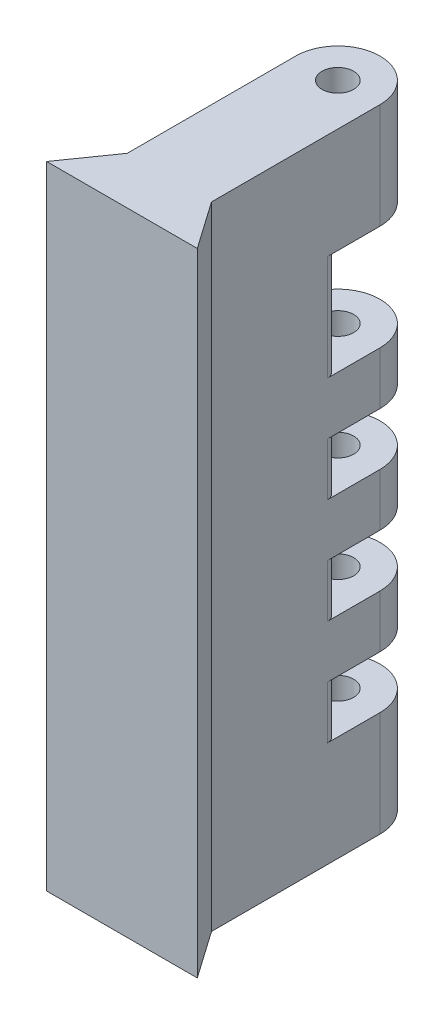
SolidWorks part; units mm, degrees
ref_plane "Front Plane" through (0, 0, 0) normal (0, 0, 1) x (1, 0, 0)
ref_plane "Top Plane" through (0, 0, 0) normal (0, 1, 0) x (1, 0, 0)
ref_plane "Right Plane" through (0, 0, 0) normal (1, 0, 0) x (0, 0, -1)
sketch "Sketch1" plane through (0, 0, 0) normal (0, 1, 0) x (1, 0, 0)
  line L0 (4, 0) -> (-4, 0)
  line L1 (-4, 0) -> (-4, -10)
  line L2 (-4, -10) -> (-4, -14.5) construction
  line L3 (-4, -10) -> (-7.1509, -14.5)
  line L4 (-7.1509, -14.5) -> (-4, -14.5)
  line L5 (0, -7.975) -> (0, 7.975) construction
  line L6 (4, -10) -> (4, -14.5) construction
  line L7 (7.1509, -14.5) -> (4, -14.5)
  line L8 (4, -10) -> (7.1509, -14.5)
  line L9 (4, 0) -> (4, -10)
  line L10 (-4, -14.5) -> (4, -14.5)
  point P12 (0, 0)
  dimension "D1" = 4
  dimension "D2" = 10
  dimension "D3" = 4.5
  dimension "D4" = 145
extrude "Boss-Extrude1" add sketch "Sketch1" along normal blind 60
sketch "Sketch2" plane through (0, 0, 0) normal (0, 1, 0) x (1, 0, 0)
  line L0 (-4, 0) -> (-4, 10)
  line L1 (4, 0) -> (4, 10)
  line L2 (4, 10) -> (-4, 10)
  line L3 (-4, 0) -> (4, 0)
  dimension "D1" = 10
sketch "Sketch3" plane through (0, 0, 0) normal (0, 1, 0) x (1, 0, 0)
  line L0 (0, 10) -> (0, 6) construction
  line L2 (4, 10) -> (-4, 10) construction
  line L3 (0, 6) -> (-4, 6) construction
  line L4 (-4, 0) -> (-4, 10) construction
  line L5 (0, 6) -> (4, 6) construction
  line L6 (4, 0) -> (4, 10) construction
  circle A0 centre (0, 6) radius 2 construction
  circle A1 centre (0, 6) radius 1.5
  dimension "D2" = 4
  dimension "D3" = 3
  dimension "D1" = 4
extrude "Boss-Extrude3" add sketch "Sketch2" along normal blind 60 contours L1 L2 L0 L3
extrude "Cut-Extrude1" cut sketch "Sketch3" along normal blind 60 contours A1
fillet "Fillet1" radius 4 2 edges at (-4, 30, -10) (4, 30, -10)
sketch "Sketch4" plane through (0, 0, 0) normal (1, 0, 0) x (0, 0, -1)
  line L0 (12.6275, 60) -> (16.8881, 60)
  line L1 (16.8881, 60) -> (16.8881, 0)
  line L2 (16.8881, 0) -> (13.4441, 0)
  line L3 (13.4441, 0) -> (13.4441, 10)
  line L4 (13.4441, 10) -> (2, 10)
  line L9 (2, 10) -> (2, 15)
  line L10 (2, 15) -> (13.4441, 15)
  line L11 (13.4441, 15) -> (13.4441, 20)
  line L12 (13.4441, 20) -> (2, 20)
  line L13 (2, 20) -> (2, 25)
  line L14 (2, 25) -> (13.4441, 25)
  line L15 (13.4441, 25) -> (13.4441, 30)
  line L16 (13.4441, 30) -> (2, 30)
  line L17 (2, 30) -> (2, 35)
  line L18 (2, 35) -> (13.4441, 35)
  line L19 (13.4441, 35) -> (13.4441, 40)
  line L20 (13.4441, 40) -> (2, 40)
  line L21 (2, 40) -> (2, 45)
  line L23 (12.6275, 60) -> (12.6275, 50)
  line L24 (12.6275, 50) -> (2, 50)
  line L25 (2, 50) -> (2, 45)
  dimension "D1" = 10
  dimension "D3" = 5
  dimension "D4" = 5
  dimension "D5" = 5
  dimension "D6" = 5
  dimension "D7" = 5
  dimension "D8" = 5
  dimension "D9" = 5
  dimension "D10" = 10
extrude "Cut-Extrude2" cut sketch "Sketch4" against normal blind 60 and the other way blind 60
fillet "Fillet3" radius 1 8 edges at (-4, 12.5, -2) (4, 12.5, -2) (4, 22.5, -2) (-4, 22.5, -2) (-4, 32.5, -2) (4, 32.5, -2) (4, 45, -2) (-4, 45, -2)
sketch "Sketch5" plane through (0, 0, 0) normal (0, 1, 0) x (1, 0, 0)
  circle A0 centre (0, 6) radius 2.6072
extrude "Boss-Extrude4" add sketch "Sketch5" along normal blind 5
